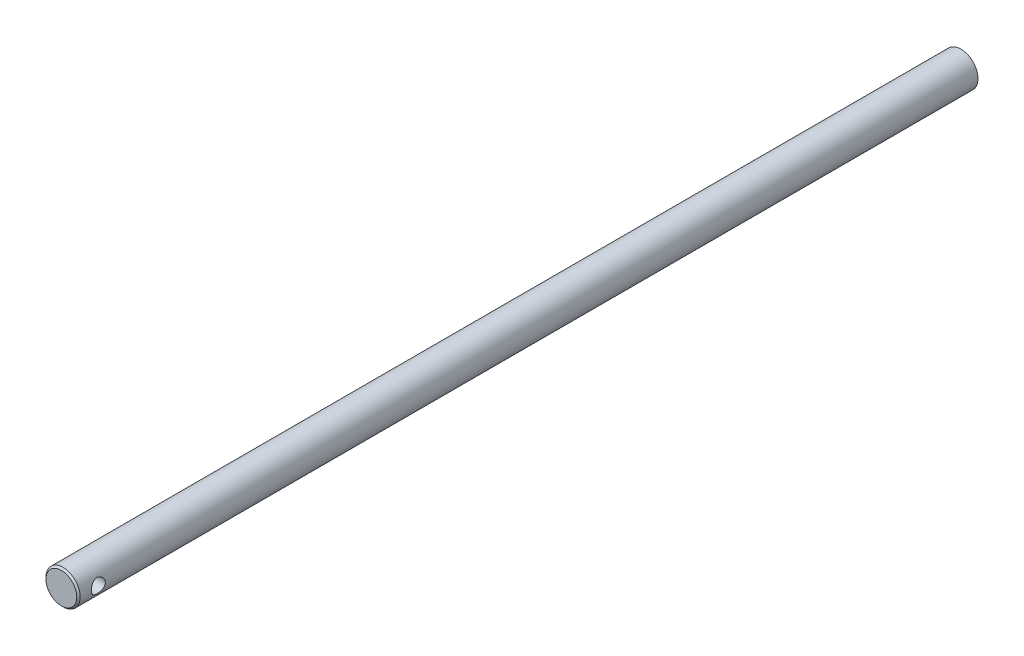
SolidWorks part; units mm, degrees
ref_plane "Спереди" through (0, 0, 0) normal (0, 0, 1) x (1, 0, 0)
ref_plane "Сверху" through (0, 0, 0) normal (0, 1, 0) x (1, 0, 0)
ref_plane "Справа" through (0, 0, 0) normal (1, 0, 0) x (0, 0, -1)
sketch "Эскиз1" plane through (0, 0, 0) normal (0, 0, 1) x (1, 0, 0)
  circle A0 centre (21, 0) radius 10
  dimension "D1" = 20
extrude "Бобышка-Вытянуть1" add sketch "Эскиз1" along normal blind 25.6 and the other way blind 500
sketch "Эскиз2" plane through (0, 0, 0) normal (1, 0, 0) x (0, 0, -1)
  line L0 (-25.6, 10) -> (-25.6, -10) construction
  line L1 (-25.6, 0) -> (-14, 0) construction
  circle A0 centre (-14, 0) radius 4.1
  dimension "D1" = 8.2
  dimension "D2" = 11.6
extrude "Вырез-Вытянуть1" cut sketch "Эскиз2" against normal through all both and the other way through all
chamfer "Фаска1" distance 1 angle 45 1 edges at (31, 0, 25.6)
